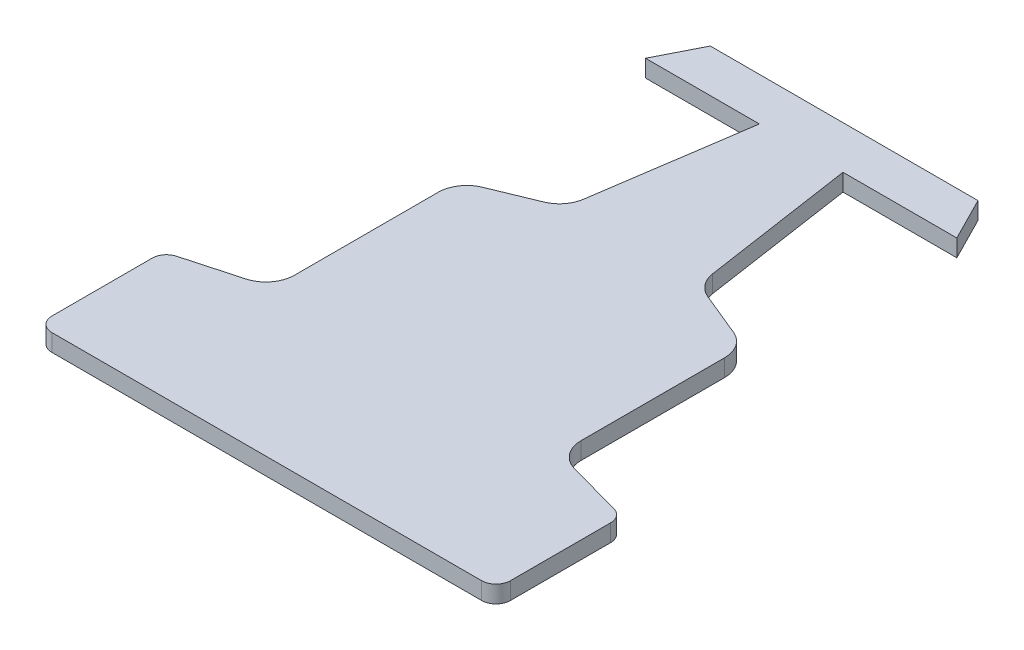
SolidWorks part; units mm, degrees
ref_plane "Front Plane" through (0, 0, 0) normal (0, 0, 1) x (1, 0, 0)
ref_plane "Top Plane" through (0, 0, 0) normal (0, 1, 0) x (1, 0, 0)
ref_plane "Right Plane" through (0, 0, 0) normal (1, 0, 0) x (0, 0, -1)
sketch "Sketch1" plane through (0, 0, 0) normal (0, 1, 0) x (1, 0, 0)
  line L1 (0, 141.6084) -> (0, -96.9346) construction
  line L4 (-57.3441, -32.0257) -> (-76.328, -37.2556)
  line L5 (-80, -42.076) -> (-80, -77.076)
  line L6 (-75, -82.076) -> (75, -82.076)
  line L27 (-50, -22.3849) -> (-50, 27.723)
  line L28 (-43.8073, 36.9699) -> (-28.6173, 43.2242)
  line L30 (-14.5952, 104.4201) -> (-54.3206, 104.4201)
  line L31 (-54.3206, 104.4201) -> (-46.7078, 119.4201)
  line L32 (-46.7078, 119.4201) -> (46.7078, 119.4201)
  line L33 (54.3206, 104.4201) -> (46.7078, 119.4201)
  line L34 (14.5952, 104.4201) -> (54.3206, 104.4201)
  line L35 (22.5332, 51.0012) -> (14.5952, 104.4201)
  line L36 (43.8073, 36.9699) -> (28.6173, 43.2242)
  line L37 (50, -22.3849) -> (50, 27.723)
  line L38 (-14.5952, 104.4201) -> (-22.5332, 51.0012)
  line L39 (80, -42.076) -> (80, -77.076)
  line L40 (57.3441, -32.0257) -> (76.328, -37.2556)
  arc A1 (80, -77.076) -> (75, -82.076) centre (75, -77.076) cw
  arc A2 (-80, -77.076) -> (-75, -82.076) centre (-75, -77.076) ccw
  arc A3 (-76.328, -37.2556) -> (-80, -42.076) centre (-75, -42.076) ccw
  arc A4 (76.328, -37.2556) -> (80, -42.076) centre (75, -42.076) cw
  arc A5 (-28.6173, 43.2242) -> (-22.5332, 51.0012) centre (-32.4246, 52.471) ccw
  arc A6 (22.5332, 51.0012) -> (28.6173, 43.2242) centre (32.4246, 52.471) ccw
  arc A7 (43.8073, 36.9699) -> (50, 27.723) centre (40, 27.723) cw
  arc A8 (57.3441, -32.0257) -> (50, -22.3849) centre (60, -22.3849) cw
  arc A9 (-50, -22.3849) -> (-57.3441, -32.0257) centre (-60, -22.3849) cw
  arc A10 (-50, 27.723) -> (-43.8073, 36.9699) centre (-40, 27.723) cw
  point P14 (0, -82.076)
  point P17 (0, -82.076)
  point P19 (0, 119.4201)
  point P24 (-23.3677, 45.3856)
  point P29 (80, -45.2283)
  point P32 (80, -82.076)
  point P35 (-80, -82.076)
  point P38 (-80, -45.2283)
  point P39 (23.3677, 45.3856)
  point P42 (50, 34.4201)
  point P45 (50, -30.0025)
  point P48 (-50, -30.0025)
  point P51 (-50, 34.4201)
  dimension "D7" = 10
  dimension "D8" = 15
  dimension "D1" = 160
  dimension "D2" = 85
  dimension "D3" = 0
  dimension "D4" = 100
  dimension "D5" = 36.8477
  dimension "D6" = 116.4961
  dimension "D9" = 93.4155
extrude "Boss-Extrude2" add sketch "Sketch1" along normal blind 6
